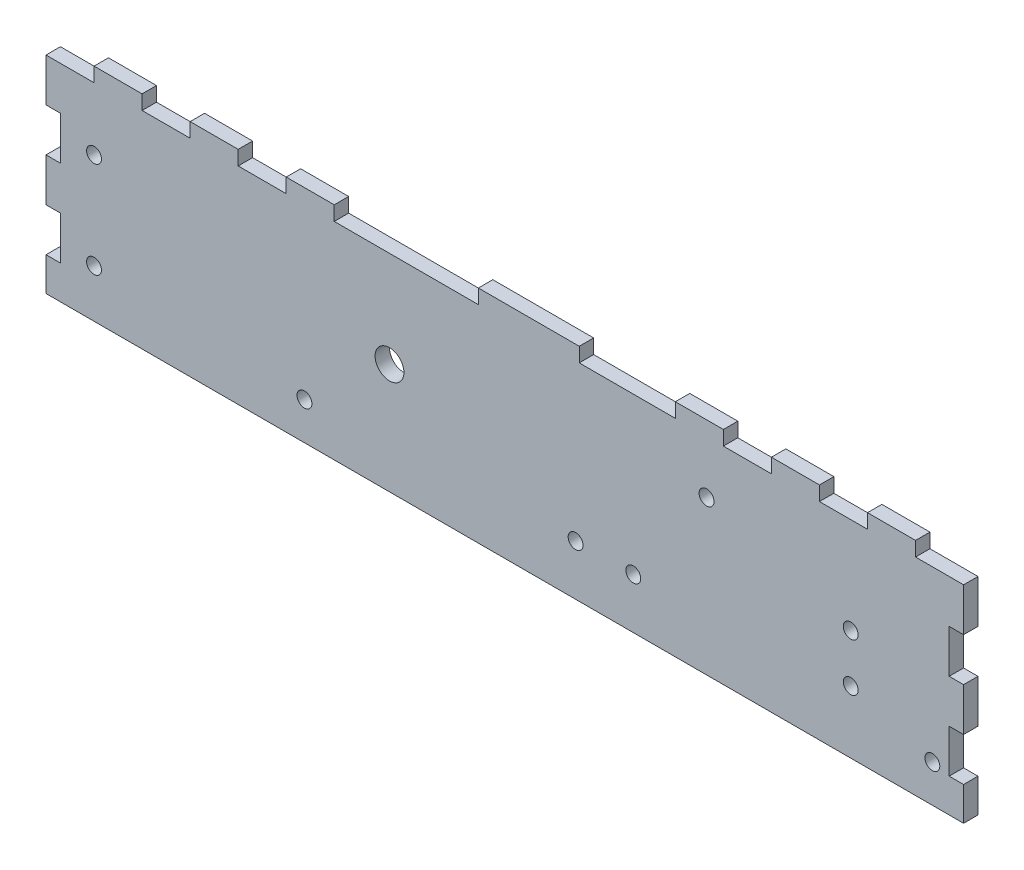
SolidWorks part; units mm, degrees
ref_plane "Front Plane" through (0, 0, 0) normal (0, 0, 1) x (1, 0, 0)
ref_plane "Top Plane" through (0, 0, 0) normal (0, 1, 0) x (1, 0, 0)
ref_plane "Right Plane" through (0, 0, 0) normal (1, 0, 0) x (0, 0, -1)
sketch "Sketch1" plane through (0, 0, 0) normal (0, 0, 1) x (1, 0, 0)
  line L4 (-191, 0) -> (0, 0)
  line L5 (0, 0) -> (0, 46)
  line L6 (0, 46) -> (-191, 46)
  line L7 (-191, 46) -> (-191, 0)
  line L8 (-191, 0) -> (0, 0)
  line L9 (0, 0) -> (0, 46)
  line L10 (0, 46) -> (-191, 46)
  line L11 (-191, 46) -> (-191, 0)
  circle A0 centre (-181, 30) radius 1.55 construction
  circle A1 centre (-181, 10) radius 1.55 construction
  circle A2 centre (-181, 30) radius 1.55
  circle A3 centre (-181, 10) radius 1.55
  dimension "D1" = 0
extrude "Boss-Extrude1" add sketch "Sketch1" along normal blind 3
sketch "Sketch5" plane through (0, 0, 3) normal (0, 0, 1) x (1, 0, 0)
  line L0 (-95.5, 0) -> (-95.5, 46) construction
  line L1 (-191, 0) -> (0, 0) construction
  line L2 (0, 46) -> (-191, 46) construction
ref_axis "Axis1" through (-95.5, 0, 3) along (0, 1, 0)
ref_plane "Plane1" through (-95.5, 0, 0) normal (1, 0, 0) x (0, 1, 0)
sketch "Sketch2" plane through (0, 0, 3) normal (0, 0, 1) x (1, 0, 0)
  line L0 (-119.5, 46) -> (-119.5, 0) construction
  line L1 (-119.5, 46) -> (-119.5, 0)
  point P2 (-119.5, 23)
ref_point "MointPoint-Sus"
sketch "Sketch3" plane through (0, 0, 0) normal (0, 0, -1) x (-1, 0, 0)
  line L4 (50, 43) -> (50, 46)
  line L5 (50, 46) -> (40, 46)
  line L6 (40, 46) -> (40, 43)
  line L7 (40, 43) -> (50, 43)
  line L8 (50, 43) -> (50, 46)
  line L9 (50, 46) -> (40, 46)
  line L10 (40, 46) -> (40, 43)
  line L11 (40, 43) -> (50, 43)
  line L12 (30, 43) -> (30, 46)
  line L13 (30, 46) -> (20, 46)
  line L14 (20, 46) -> (20, 43)
  line L15 (20, 43) -> (30, 43)
  line L16 (30, 43) -> (30, 46)
  line L17 (30, 46) -> (20, 46)
  line L18 (20, 46) -> (20, 43)
  line L19 (20, 43) -> (30, 43)
  line L20 (10, 43) -> (10, 46)
  line L21 (10, 46) -> (0, 46)
  line L22 (0, 46) -> (0, 43)
  line L23 (0, 43) -> (10, 43)
  line L24 (10, 43) -> (10, 46)
  line L25 (10, 46) -> (0, 46)
  line L26 (0, 46) -> (0, 43)
  line L27 (0, 43) -> (10, 43)
  line L28 (171, 43) -> (171, 46)
  line L29 (171, 46) -> (161, 46)
  line L30 (161, 46) -> (161, 43)
  line L31 (161, 43) -> (171, 43)
  line L32 (171, 43) -> (171, 46)
  line L33 (171, 46) -> (161, 46)
  line L34 (161, 46) -> (161, 43)
  line L35 (161, 43) -> (171, 43)
  line L36 (151, 43) -> (151, 46)
  line L37 (151, 46) -> (141, 46)
  line L38 (141, 46) -> (141, 43)
  line L39 (141, 43) -> (151, 43)
  line L40 (151, 43) -> (151, 46)
  line L41 (151, 46) -> (141, 46)
  line L42 (141, 46) -> (141, 43)
  line L43 (141, 43) -> (151, 43)
  line L44 (131, 46) -> (101, 46)
  line L45 (101, 46) -> (101, 43)
  line L46 (101, 43) -> (131, 43)
  line L47 (131, 43) -> (131, 46)
  line L48 (131, 46) -> (101, 46)
  line L49 (101, 46) -> (101, 43)
  line L50 (101, 43) -> (131, 43)
  line L51 (131, 43) -> (131, 46)
  line L52 (80, 46) -> (60, 46)
  line L53 (80, 43) -> (80, 46)
  line L54 (60, 43) -> (80, 43)
  line L55 (60, 46) -> (60, 43)
  line L56 (80, 46) -> (60, 46)
  line L57 (80, 43) -> (80, 46)
  line L58 (60, 43) -> (80, 43)
  line L59 (60, 46) -> (60, 43)
  line L60 (181, 43) -> (191, 43)
  line L61 (181, 46) -> (181, 43)
  line L62 (191, 46) -> (181, 46)
  line L63 (191, 43) -> (191, 46)
  line L64 (181, 43) -> (191, 43)
  line L65 (181, 46) -> (181, 43)
  line L66 (191, 46) -> (181, 46)
  line L67 (191, 43) -> (191, 46)
  dimension "D1" = 0
  dimension "D2" = 0
  dimension "D3" = 0
  dimension "D4" = 0
  dimension "D5" = 0
  dimension "D6" = 0
  dimension "D7" = 0
  dimension "D8" = 0
extrude "Cut-Extrude1" cut sketch "Sketch3" against normal up to next
sketch "Sketch4" plane through (0, 0, 3) normal (0, 0, 1) x (1, 0, 0)
  line L0 (-3, 43) -> (-3, 0) construction
  line L1 (0, 43) -> (-10, 43) construction
  line L2 (-191, 0) -> (0, 0) construction
  line L3 (0, 0) -> (0, 43) construction
  line L4 (-3, 34) -> (0, 34)
  line L5 (-3, 25) -> (0, 25)
  line L6 (-3, 16) -> (0, 16)
  line L7 (-3, 7) -> (0, 7)
  line L8 (0, 34) -> (0, 25)
  line L9 (-3, 25) -> (-3, 34)
  line L10 (0, 16) -> (0, 7)
  line L11 (-3, 7) -> (-3, 16)
  dimension "D1" = 3
  dimension "D2" = 9
  dimension "D3" = 4
extrude "Cut-Extrude2" cut sketch "Sketch4" against normal up to next
mirror "Mirror1" about plane through (-95.5, 0, 0) normal (1, 0, 0) of "Cut-Extrude2"
sketch "Sketch6" plane through (0, 0, 3) normal (0, 0, 1) x (1, 0, 0)
  circle A0 centre (-119.5, 23) radius 3
  point P0 (-119.5, 23)
  dimension "D1" = 6
extrude "Cut-Extrude3" cut sketch "Sketch6" against normal up to next
sketch "Sketch7" plane through (0, 0, 3) normal (0, 0, 1) x (1, 0, 0)
  circle A0 centre (-53.5, 32) radius 1.55 construction
  circle A1 centre (-68.7574, 10.5) radius 1.55 construction
  circle A2 centre (-80.7574, 10.5) radius 1.55 construction
  circle A3 centre (-23.5, 23) radius 1.55 construction
  circle A4 centre (-23.5, 13) radius 1.55 construction
  circle A5 centre (-53.5, 32) radius 1.55
  circle A6 centre (-68.7574, 10.5) radius 1.55
  circle A7 centre (-80.7574, 10.5) radius 1.55
  circle A8 centre (-23.5, 23) radius 1.55
  circle A9 centre (-23.5, 13) radius 1.55
extrude "Cut-Extrude4" cut sketch "Sketch7" against normal up to next
sketch "Sketch8" plane through (0, 0, 0) normal (0, 0, -1) x (-1, 0, 0)
  circle A0 centre (137.2, 7.8) radius 1.55 construction
  circle A1 centre (6.5, 7.8) radius 1.55 construction
  circle A2 centre (137.2, 7.8) radius 1.55
  circle A3 centre (6.5, 7.8) radius 1.55
extrude "Cut-Extrude5" cut sketch "Sketch8" against normal up to next
